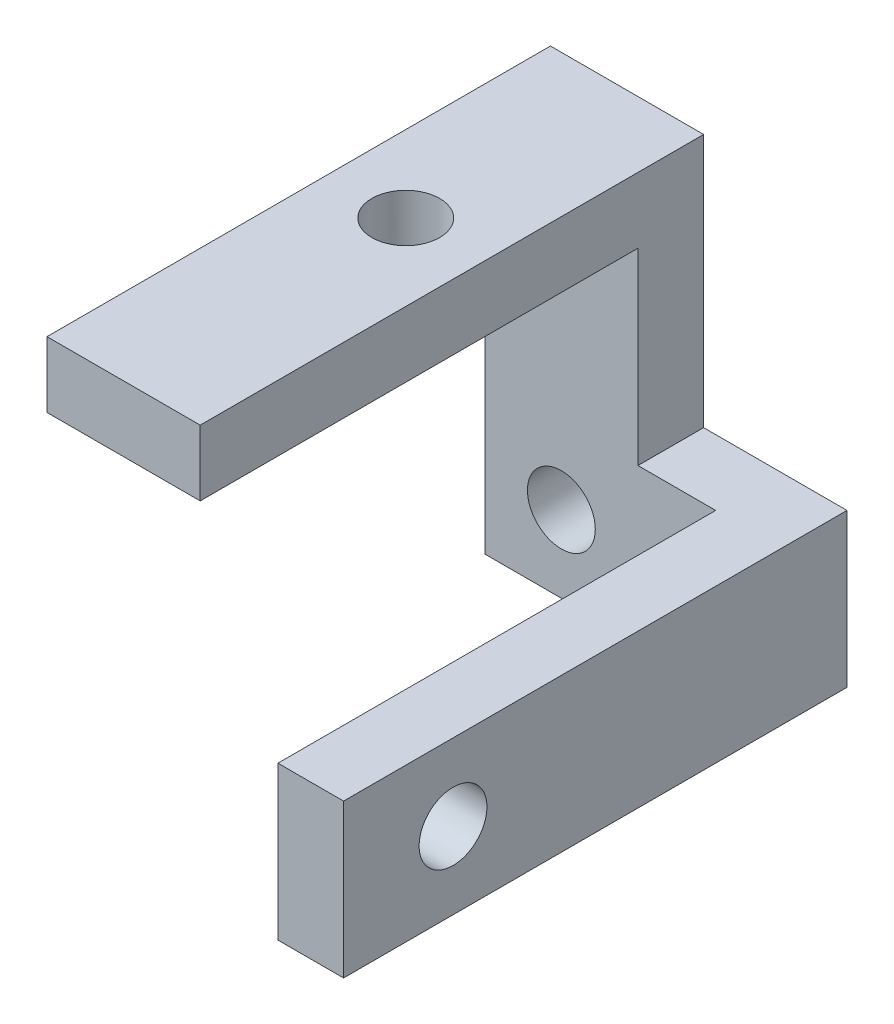
SolidWorks part; units mm, degrees
ref_plane "Plan de face" through (0, 0, 0) normal (0, 0, 1) x (1, 0, 0)
ref_plane "Plan de dessus" through (0, 0, 0) normal (0, 1, 0) x (1, 0, 0)
ref_plane "Plan de droite" through (0, 0, 0) normal (1, 0, 0) x (0, 0, -1)
sketch "Esquisse1" plane through (0, 0, 0) normal (0, 0, 1) x (1, 0, 0)
  line L1 (0, 0) -> (7, 0)
  line L2 (0, 0) -> (0, 18.6)
  line L3 (0, 18.6) -> (7, 18.6)
  line L4 (7, 0) -> (7, 18.6)
  line L5 (0, 7) -> (13.55, 7)
  line L6 (0, 7) -> (0, 0)
  line L7 (0, 0) -> (13.55, 0)
  line L8 (13.55, 7) -> (13.55, 0)
  dimension "D1" = 18.6
  dimension "D2" = 13.55
  dimension "D3" = 7
  dimension "D4" = 7
extrude "Boss.-Extru.1" add sketch "Esquisse1" along normal blind 3 contours L2 L5 L4 L3 | L5 L2 L1 L4 | L8 L5 L4 L7 region at (3.5, 3.5, 0) region at (10.275, 3.5, 0) region at (3.5, 12.8, 0)
sketch "Esquisse2" plane through (0, 0, 3) normal (0, 0, 1) x (1, 0, 0)
  line L0 (7, 7) -> (7, 18.6) construction
  line L1 (0, 18.6) -> (7, 18.6)
  line L2 (0, 18.6) -> (0, 15.6)
  line L3 (0, 15.6) -> (7, 15.6)
  line L4 (7, 18.6) -> (7, 15.6)
  dimension "D1" = 3
extrude "Boss.-Extru.2" add sketch "Esquisse2" along normal blind 20
sketch "Esquisse3" plane through (0, 0, 3) normal (0, 0, 1) x (1, 0, 0)
  line L0 (0, 0) -> (13.55, 0) construction
  line L1 (13.55, 7) -> (10.55, 7)
  line L2 (13.55, 7) -> (13.55, 0)
  line L3 (13.55, 0) -> (10.55, 0)
  line L4 (10.55, 7) -> (10.55, 0)
  dimension "D1" = 3
extrude "Boss.-Extru.3" add sketch "Esquisse3" along normal blind 20
sketch "Esquisse4" plane through (0, 15.6, 0) normal (0, -1, 0) x (1, 0, 0)
  line L0 (0, 23) -> (7, 23) construction
  line L1 (7, 23) -> (7, 3) construction
  circle A0 centre (3.5, 10.11) radius 1.55
  point P6 (0, 0)
  dimension "D1" = 3.1
  dimension "D2" = 12.89
  dimension "D3" = 3.5
sketch "Esquisse5" plane through (10.55, 0, 0) normal (-1, 0, 0) x (0, 0, 1)
  line L0 (23, 7) -> (3, 7) construction
  line L1 (23, 7) -> (23, 0) construction
  circle A0 centre (18, 3.5) radius 1.55
  dimension "D1" = 3.5
  dimension "D2" = 3.1
  dimension "D3" = 5
extrude "Enlèv. mat.-Extru.1" cut sketch "Esquisse4" against normal blind 20
extrude "Enlèv. mat.-Extru.2" cut sketch "Esquisse5" against normal blind 20
sketch "Esquisse6" plane through (0, 0, 3) normal (0, 0, 1) x (1, 0, 0)
  line L0 (0, 0) -> (0, 15.6) construction
  line L1 (0, 0) -> (10.55, 0) construction
  circle A0 centre (3.5, 3.5) radius 1.55
  dimension "D1" = 3.1
  dimension "D2" = 3.5
  dimension "D3" = 3.5
extrude "Enlèv. mat.-Extru.3" cut sketch "Esquisse6" against normal blind 20
